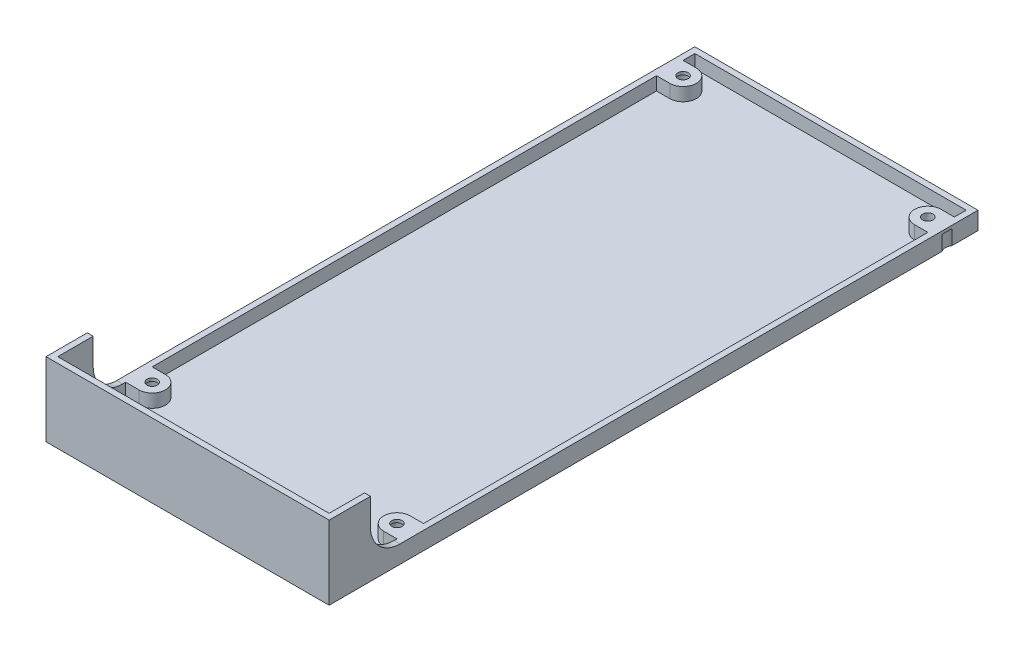
SolidWorks part; units mm, degrees
ref_plane "Front Plane" through (0, 0, 0) normal (0, 0, 1) x (1, 0, 0)
ref_plane "Top Plane" through (0, 0, 0) normal (0, 1, 0) x (1, 0, 0)
ref_plane "Right Plane" through (0, 0, 0) normal (1, 0, 0) x (0, 0, -1)
sketch "Sketch1" plane through (0, 0, 0) normal (0, 1, 0) x (1, 0, 0)
  line L1 (0, 5.4678) -> (96, 5.4678)
  line L2 (0, 5.4678) -> (0, 225.4678)
  line L3 (0, 225.4678) -> (96, 225.4678)
  line L4 (96, 5.4678) -> (96, 225.4678)
  dimension "D1" = 220
  dimension "D2" = 96
extrude "Boss-Extrude1" add sketch "Sketch1" along normal blind 25
sketch "Sketch2" plane through (0, 25, 0) normal (0, 1, 0) x (1, 0, 0)
  line L0 (2, 223.4678) -> (2, 219.4678)
  line L1 (2, 7.4678) -> (94, 7.4678)
  line L2 (94, 7.4678) -> (94, 30.4678)
  line L3 (94, 223.4678) -> (2, 223.4678)
  line L4 (0, 225.4678) -> (0, 5.4678)
  line L5 (0, 5.4678) -> (96, 5.4678)
  line L6 (96, 5.4678) -> (96, 225.4678)
  line L7 (96, 225.4678) -> (0, 225.4678)
  line L8 (0, 225.4678) -> (0, 5.4678)
  line L9 (0, 5.4678) -> (96, 5.4678)
  line L10 (96, 5.4678) -> (96, 225.4678)
  line L11 (96, 225.4678) -> (0, 225.4678)
  line L12 (94, 39.4678) -> (89.5, 39.4678)
  line L13 (89.5, 210.4678) -> (94, 210.4678)
  line L14 (89.5, 219.4678) -> (94, 219.4678)
  line L15 (6.5, 219.4678) -> (2, 219.4678)
  line L16 (6.5, 210.4678) -> (2, 210.4678)
  line L17 (6.5, 30.4678) -> (2, 30.4678)
  line L18 (6.5, 39.4678) -> (2, 39.4678)
  line L19 (2, 30.4678) -> (2, 7.4678)
  line L20 (89.5, 30.4678) -> (94, 30.4678)
  line L21 (2, 223.4678) -> (2, 7.4678) construction
  line L22 (94, 39.4678) -> (94, 210.4678)
  line L23 (94, 219.4678) -> (94, 223.4678)
  line L24 (94, 7.4678) -> (94, 223.4678) construction
  line L25 (2, 210.4678) -> (2, 39.4678)
  arc A0 (6.5, 210.4678) -> (6.5, 219.4678) centre (6.5, 214.9678) ccw
  arc A1 (89.5, 219.4678) -> (89.5, 210.4678) centre (89.5, 214.9678) ccw
  arc A2 (6.5, 30.4678) -> (6.5, 39.4678) centre (6.5, 34.9678) ccw
  arc A3 (89.5, 39.4678) -> (89.5, 30.4678) centre (89.5, 34.9678) ccw
  dimension "D3" = 9
  dimension "D4" = 6.5
  dimension "D5" = 6.5
  dimension "D7" = 180
  dimension "D6" = 10.5
  dimension "D1" = 0
  dimension "D2" = 2
extrude "Cut-Extrude1" cut sketch "Sketch2" against normal blind 23.5 contours L12 A3 L20 L2 L1 L19 L17 A2 L18 L25 L16 A0 L15 L0 L3 L23 L14 A1 L13 L22
sketch "Sketch3" plane through (96, 0, 0) normal (1, 0, 0) x (0, 0, -1)
  line L0 (225.4678, 6) -> (29.4678, 6)
  line L1 (225.4678, 25) -> (225.4678, 0) construction
  line L3 (19.4678, 25) -> (19.4678, 16)
  line L4 (5.4678, 25) -> (225.4678, 25) construction
  line L5 (19.4678, 25) -> (225.4678, 25)
  line L6 (225.4678, 25) -> (225.4678, 6)
  line L7 (5.4678, 0) -> (225.4678, 0) construction
  line L8 (5.4678, 25) -> (5.4678, 0) construction
  arc A0 (29.4678, 6) -> (19.4678, 16) centre (29.4678, 16) cw
  dimension "D1" = 10
  dimension "D2" = 6
  dimension "D3" = 14
extrude "Cut-Extrude2" cut sketch "Sketch3" against normal up to surface (96 mm away) up to face at (0, 12.5, -115.4678)
sketch "Sketch4" plane through (0, 6, 0) normal (0, 1, 0) x (1, 0, 0)
  circle A0 centre (6.5, 34.9678) radius 1.75
  circle A1 centre (89.5, 34.9678) radius 1.75
  circle A2 centre (89.5, 214.9678) radius 1.75
  circle A3 centre (6.5, 214.9678) radius 1.75
  dimension "D1" = 3.5
extrude "Cut-Extrude3" cut sketch "Sketch4" against normal up to next
sketch "Sketch5" plane through (0, 0, 0) normal (0, -1, 0) x (1, 0, 0)
  circle A0 centre (6.5, -34.9678) radius 3
  circle A1 centre (89.5, -34.9678) radius 3
  circle A2 centre (6.5, -214.9678) radius 3
  circle A3 centre (98.5, -214.9678) radius 3
  dimension "D1" = 6
extrude "Cut-Extrude4" cut sketch "Sketch5" against normal blind 5
